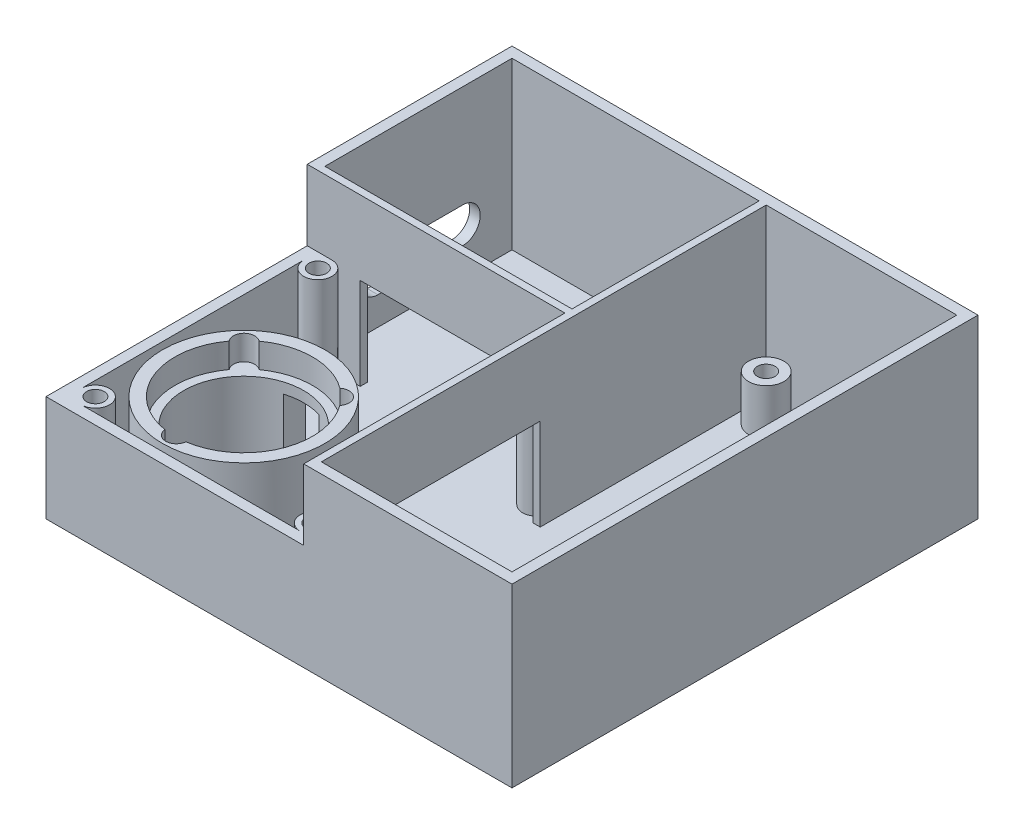
SolidWorks part; units mm, degrees
note: The reader was unsure of these and kept them because the rebuilt part matched: shared geometry of " 指纹头<7>", "草图1<5>", "草图1<6>", "草图1<7>", "草图1<9>".
ref_plane "前视基准面" through (0, 0, 0) normal (0, 0, 1) x (1, 0, 0)
ref_plane "上视基准面" through (0, 0, 0) normal (0, 1, 0) x (1, 0, 0)
ref_plane "右视基准面" through (0, 0, 0) normal (1, 0, 0) x (0, 0, -1)
sketch " 指纹头" plane through (0, 0, 0) normal (0, 1, 0) x (1, 0, 0)
  circle A0 centre (14, 14) radius 9.75
  circle A1 centre (14, 14) radius 11.5
  arc A2 (12.4664, 4.3714) -> (15.4538, 4.359) centre (13.9607, 4.5026) ccw
  arc A3 (21.8929, 19.7241) -> (19.7892, 21.8452) centre (20.7435, 20.6879) ccw
  circle A4 centre (14, 14) radius 9.75
  arc A5 (8.2759, 21.8929) -> (6.1548, 19.7892) centre (7.3121, 20.7435) ccw
  circle A6 centre (14, 14) radius 8.5
  circle A7 centre (14, 14) radius 9.75
  point P5 (14.2465, 16.554)
  dimension "D1" = 19.5
  dimension "D2" = 23
  dimension "D5" = 1.5
  dimension "D9" = 17
  dimension "D3" = 2
  dimension "D4" = 14
  dimension "D6" = 2.9874
  dimension "D8" = 14
  dimension "D7" = 2
sketch "草图1" plane through (0, 0, 0) normal (0, 1, 0) x (1, 0, 0)
  line L0 (1.5, 1.5) -> (1.5, 64.5)
  line L1 (0, 0) -> (66, 0)
  line L2 (0, 0) -> (0, 66)
  line L3 (0, 66) -> (66, 66)
  line L4 (66, 0) -> (66, 66)
  line L5 (1.5, 64.5) -> (64.5, 64.5)
  line L6 (64.5, 1.5) -> (64.5, 64.5)
  line L7 (1.5, 1.5) -> (36.5, 1.5)
  line L8 (1.5, 38) -> (36.5, 38)
  line L9 (36.5, 38) -> (36.5, 64.5)
  line L10 (1.5, 37) -> (36.5, 37)
  line L11 (37.5, 37) -> (37.5, 64.5)
  line L12 (37.5, 37) -> (37.5, 1.5)
  line L13 (36.5, 37) -> (36.5, 1.5)
  line L14 (36.5, 1.5) -> (37.5, 1.5)
  line L15 (1.5, 37) -> (37.5, 37) construction
  line L16 (37.5, 1.5) -> (64.5, 1.5)
  line L17 (1.5, 37) -> (0, 37)
  line L18 (1.5, 1.5) -> (64.5, 1.5) construction
  line L19 (36.5, 1.5) -> (36.5, 0)
  circle A0 centre (40.9, 61.1) radius 1.25
  circle A1 centre (40.9, 61.1) radius 2.5
  circle A2 centre (61.1, 61.1) radius 1.25
  circle A3 centre (61.1, 61.1) radius 2.5
  circle A4 centre (61.1, 15.6) radius 1.25
  circle A5 centre (61.1, 15.6) radius 2.5
  circle A6 centre (40.9, 15.6) radius 1.25
  circle A7 centre (40.9, 15.6) radius 2.5
  circle A8 centre (3.5, 3.5) radius 1.25
  circle A9 centre (3.5, 3.5) radius 2
  circle A10 centre (34.5, 3.5) radius 1.25
  circle A11 centre (34.5, 3.5) radius 2
  circle A12 centre (34.5, 35) radius 1.25
  circle A13 centre (34.5, 35) radius 2
  circle A14 centre (3.5, 35) radius 1.25
  circle A15 centre (3.5, 35) radius 2
  dimension "D8" = 2.5
  dimension "D9" = 5
  dimension "D10" = 3.4
  dimension "D16" = 2.5
  dimension "D17" = 4
  dimension "D1" = 66
  dimension "D2" = 66
  dimension "D4" = 35
  dimension "D5" = 26.5
  dimension "D7" = 27
  dimension "D11" = 3.4
  dimension "D14" = 3.4
  dimension "D15" = 14.1
  dimension "D18" = 3.5
  dimension "D19" = 3.5
  dimension "D3" = 1.5
  dimension "D6" = 1
  dimension "D12" = 2
  dimension "D13" = 2
  dimension "D20" = 2
  dimension "D21" = 2
extrude "凸台-拉伸6" add sketch " 指纹头" along normal blind 11.5
extrude "凸台-拉伸7" add sketch " 指纹头<7>" along normal blind 15
sketch " 指纹头<7>" plane through (0, 0, 0) normal (0, 1, 0) x (1, 0, 0) same geometry as " 指纹头"
ref_plane "基准面1" through (0, 0, -20) normal (0, 0, 1) x (1, 0, 0)
sketch "草图4" plane through (0, 0, -20) normal (0, 0, 1) x (1, 0, 0)
  line L0 (19.7892, 15) -> (8.2759, 15) construction
  line L1 (16.5326, 10) -> (11.5326, 10)
  line L2 (16.5326, 10) -> (16.5326, 0)
  line L3 (16.5326, 0) -> (11.5326, 0)
  line L4 (11.5326, 10) -> (11.5326, 0)
  line L8 (2.5, 0) -> (25.5, 0) construction
  point P4 (14.0326, 10)
  point P7 (14.0326, 15)
  dimension "D1" = 10
  dimension "D2" = 5
extrude "切除-拉伸1" cut sketch "草图4" against normal up to next
extrude "凸台-拉伸8" add sketch "草图1" along normal blind 1.5 contours L8 L9 L5 L0 | L12 L16 L6 L5 L11 | L13 L10 L0 L7
extrude "凸台-拉伸9" add sketch "草图1<5>" along normal blind 25 contours L1 L4 L3 L2 L16 L14 L7 L0 L5 L6 | L13 L14 L12 L11 L5 L9 L8 L0 L10
sketch "草图1<5>" plane through (0, 0, 0) normal (0, 1, 0) x (1, 0, 0) same geometry as "草图1"
extrude "凸台-拉伸10" add sketch "草图1<6>" along normal blind 8 contours A3 A2 | A1 A0 | A7 A6 | A5 A4
sketch "草图1<6>" plane through (0, 0, 0) normal (0, 1, 0) x (1, 0, 0) same geometry as "草图1"
extrude "凸台-拉伸11" add sketch "草图1<7>" along normal blind 15 contours L19 L7 L0 L17 L2 L1
sketch "草图1<7>" plane through (0, 0, 0) normal (0, 1, 0) x (1, 0, 0) same geometry as "草图1"
extrude "凸台-拉伸22" add sketch "草图1<9>" along normal blind 15 contours A9 A8 | A9 L0 L7 | A11 A10 | A11 L7 L13 | A13 A12 | A13 L13 L10 | A15 A14 | A15 L10 L0
sketch "草图1<9>" plane through (0, 0, 0) normal (0, 1, 0) x (1, 0, 0) same geometry as "草图1"
sketch "草图5" plane through (36.5, 0, 0) normal (-1, 0, 0) x (0, 0, 1)
  line L0 (-35, 1.5) -> (-3.5, 1.5) construction
  line L6 (-4.5, 1.5) -> (-32.5, 1.5)
  line L7 (-4.5, 1.5) -> (-4.5, 14.5)
  line L8 (-4.5, 14.5) -> (-32.5, 14.5)
  line L9 (-32.5, 1.5) -> (-32.5, 14.5)
  line L10 (-1.5, 25) -> (-1.5, 1.5) construction
  dimension "D1" = 28
  dimension "D2" = 13
  dimension "D3" = 3
extrude "切除-拉伸2" cut sketch "草图5" against normal up to next
sketch "草图6" plane through (0, 0, -37) normal (0, 0, 1) x (1, 0, 0)
  line L0 (36.5, 25) -> (36.5, 15) construction
  line L1 (32.5, 1.5) -> (7.5, 1.5)
  line L2 (32.5, 1.5) -> (32.5, 14.5)
  line L3 (32.5, 14.5) -> (7.5, 14.5)
  line L4 (7.5, 1.5) -> (7.5, 14.5)
  line L5 (3.5, 1.5) -> (34.5, 1.5) construction
  dimension "D1" = 13
  dimension "D2" = 25
  dimension "D3" = 4
extrude "切除-拉伸3" cut sketch "草图6" against normal up to next
sketch "草图7" plane through (0, 0, 0) normal (-1, 0, 0) x (0, 0, 1)
  line L0 (-57.5, 8) -> (-45.5, 8) construction
  line L1 (-57.5, 10.5) -> (-45.5, 10.5)
  line L2 (-57.5, 5.5) -> (-45.5, 5.5)
  line L3 (-38, 1.5) -> (-64.5, 1.5) construction
  line L4 (-37, 25) -> (-66, 25) construction
  line L5 (-37, 25) -> (-66, 25)
  arc A0 (-57.5, 10.5) -> (-57.5, 5.5) centre (-57.5, 8) ccw
  arc A1 (-45.5, 5.5) -> (-45.5, 10.5) centre (-45.5, 8) ccw
  point P2 (-51.5, 8)
  point P11 (-51.5, 25)
  point P12 (-58.103, 8)
  dimension "D3" = 12
  dimension "D1" = 4
  dimension "D2" = 5
extrude "切除-拉伸4" cut sketch "草图7" against normal up to next
